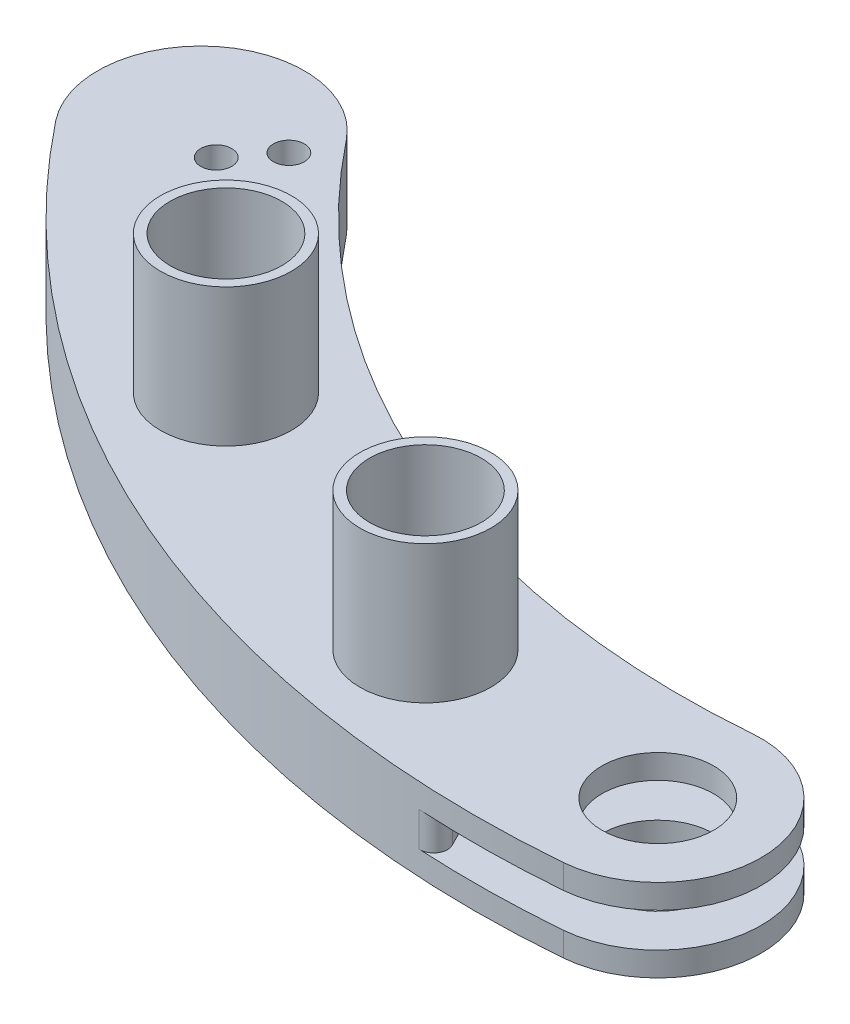
SolidWorks part; units mm, degrees
ref_plane "Front Plane" through (0, 0, 0) normal (0, 0, 1) x (1, 0, 0)
ref_plane "Top Plane" through (0, 0, 0) normal (0, 1, 0) x (1, 0, 0)
ref_plane "Right Plane" through (0, 0, 0) normal (1, 0, 0) x (0, 0, -1)
sketch "Sketch1" plane through (0, 0, 0) normal (0, 1, 0) x (1, 0, 0)
  arc A0 (0, 0) -> (-117, 50.7404) centre (-11.1561, 134.5383) cw construction
  arc A1 (-128.7604, 41.4296) -> (1.2396, -14.9487) centre (-11.1561, 134.5383) ccw
  arc A2 (-105.2396, 60.0513) -> (-1.2396, 14.9487) centre (-11.1561, 134.5383) ccw
  arc A3 (-105.2396, 60.0513) -> (-128.7604, 41.4296) centre (-117, 50.7404) ccw
  arc A4 (1.2396, -14.9487) -> (-1.2396, 14.9487) centre (0, 0) ccw
  arc A5 (-16.6792, 14.6654) -> (-15.4249, -15.401) centre (4.9458, 0.5082) ccw
  point P3 (-64.8692, 10.6839)
  dimension "D3" = 30
  dimension "D4" = 150
  dimension "D1" = 75
  dimension "D2" = 130
extrude "Boss-Extrude4" add sketch "Sketch1" along normal blind 12 contours A5 A2 A3 A1 region at (-76.6272, 0, -21.3687)
extrude "Boss-Extrude5" add sketch "Sketch1<6>" along normal blind 3.5 contours A2 A5 A1 A4 region at (-3.6374, 0, 0.1249)
sketch "Sketch1<6>" plane through (0, 0, 0) normal (0, 1, 0) x (1, 0, 0) same geometry as "Sketch1"
extrude "Boss-Extrude6" add sketch "Sketch1<8>" along normal blind 12 contours A2 A5 A1 A4 region at (-3.6374, 0, 0.1249)
sketch "Sketch1<8>" plane through (0, 0, 0) normal (0, 1, 0) x (1, 0, 0) same geometry as "Sketch1"
extrude "Cut-Extrude2" cut sketch "Sketch1<9>" along normal blind 8.5 contours A2 A5 A1 A4 region at (-3.6374, 0, 0.1249)
sketch "Sketch1<9>" plane through (0, 0, 0) normal (0, 1, 0) x (1, 0, 0) same geometry as "Sketch1"
extrude "Boss-Extrude7" add sketch "Sketch1<10>" along normal blind 3.5 contours A2 A5 A1 A4 region at (-3.6374, 0, 0.1249)
sketch "Sketch1<10>" plane through (0, 0, 0) normal (0, 1, 0) x (1, 0, 0) same geometry as "Sketch1"
sketch "Sketch2" plane through (0, 12, 0) normal (0, 1, 0) x (1, 0, 0)
  circle A0 centre (0, 0) radius 8.1
  dimension "D1" = 16.2
extrude "Cut-Extrude3" cut sketch "Sketch2" against normal blind 12
fillet "Fillet1" radius 5 1 edges at (-16.6792, 6, -14.6654)
fillet "Fillet2" radius 2 1 edges at (-15.4249, 6, 15.401)
sketch "Sketch3" plane through (0, 12, 0) normal (0, 1, 0) x (1, 0, 0)
  circle A0 centre (-107.8166, 54.3025) radius 2.25
  circle A1 centre (-112.4991, 48.4438) radius 2.25
  point P4 (0, 0)
  dimension "D1" = 4.5
  dimension "D2" = 4.5
  dimension "D3" = 7.5
  dimension "D4" = 6.3
extrude "Cut-Extrude4" cut sketch "Sketch3" against normal blind 12
sketch "Sketch4" plane through (0, 12, 0) normal (0, 1, 0) x (1, 0, 0)
  circle A0 centre (-35.5199, 1.812) radius 8.1
  circle A1 centre (-35.5199, 1.812) radius 9.5
  circle A2 centre (-82.2472, 19.6043) radius 8.1
  circle A3 centre (-82.2472, 19.6043) radius 9.5
  dimension "D1" = 16.2
  dimension "D2" = 19
  dimension "D3" = 50
extrude "Boss-Extrude8" add sketch "Sketch4" along normal blind 20
